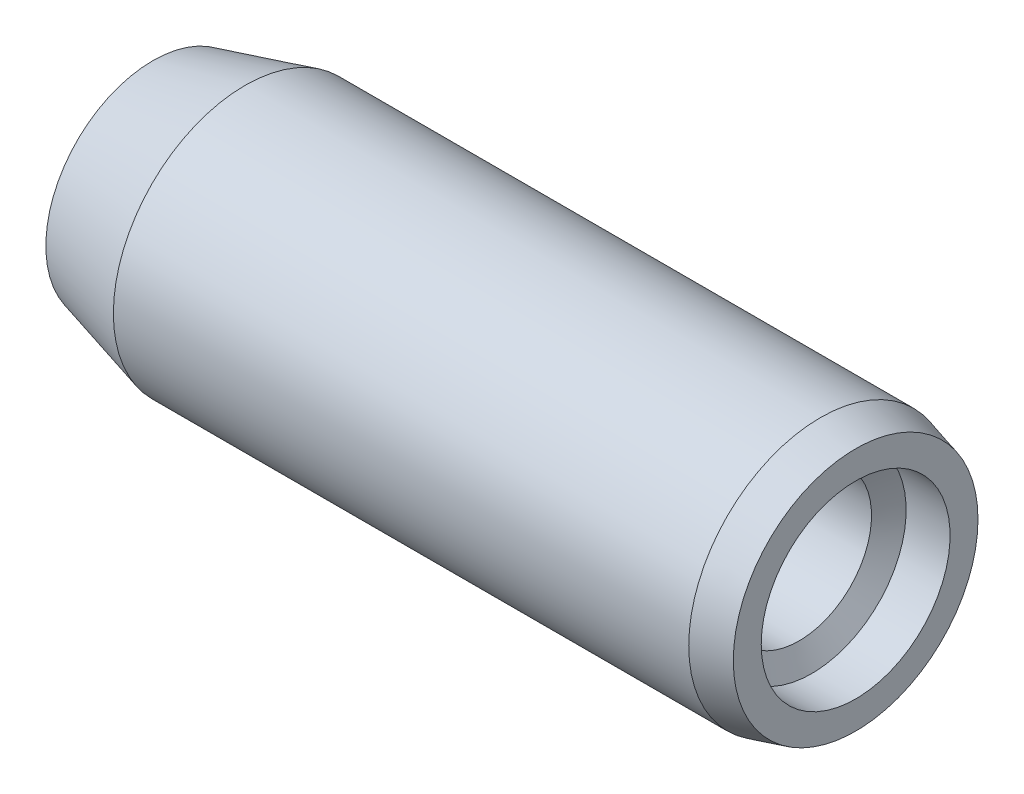
SolidWorks part; units mm, degrees
ref_plane "Front" through (0, 0, 0) normal (0, 0, 1) x (1, 0, 0)
ref_plane "Top" through (0, 0, 0) normal (0, 1, 0) x (1, 0, 0)
ref_plane "Right" through (0, 0, 0) normal (1, 0, 0) x (0, 0, -1)
sketch "Sketch1" plane through (0, 0, 0) normal (0, 0, 1) x (1, 0, 0)
  line L0 (0.5904, 2.5955) -> (0.5904, 0) construction
  line L1 (-3.8625, 0) -> (2.9703, 0) construction
  line L3 (0.5904, 2.5955) -> (2.1, 3)
  line L4 (2.1, 3) -> (15.2, 3)
  line L5 (15.2, 3) -> (16, 2.7856)
  line L6 (16, 2.7856) -> (16, 0)
  line L7 (16, 0) -> (0, 0)
  arc A0 (0.5904, 2.5955) -> (0, 0) centre (6, 0) ccw
  dimension "D1" = 6
  dimension "D3" = 15
  dimension "D7" = 75
revolve "Base-Revolve" add sketch "Sketch1" angle 360 about L1
sketch "Sketch2" plane through (0, 0, 0) normal (0, 0, 1) x (1, 0, 0)
  line L0 (0, 0) -> (0, 2.4373)
  line L1 (0, 2.4373) -> (2.1, 3)
  line L2 (2.1, 3) -> (15.2, 3)
  line L3 (15.2, 3) -> (16, 2.7856)
  line L4 (16, 2.7856) -> (16, 0)
  line L5 (16, 0) -> (0, 0)
  line L6 (0, 0) -> (-16.9805, 0) construction
  dimension "D1" = 6
  dimension "D2" = 15
  dimension "D3" = 75
  dimension "D4" = 16
  dimension "D5" = 0.8
  dimension "D6" = 2.1
revolve "Base-Revolve2" add sketch "Sketch2" angle 360 about L6
sketch "Sketch3" plane through (0, 0, 0) normal (0, 0, 1) x (1, 0, 0)
  line L0 (16, 0) -> (16, 2.15) construction
  line L1 (16, 2.15) -> (16.2, 2.15)
  line L2 (16, 2.15) -> (15, 2.15)
  line L3 (15, 2.15) -> (14.7113, 1.65)
  line L4 (14.7113, 1.65) -> (6, 1.65)
  line L5 (6, 1.65) -> (5.0474, 0)
  line L6 (5.0474, 0) -> (16, 0)
  line L7 (16, 0) -> (16.7399, 0) construction
  line L8 (16.2, 2.15) -> (16.2, 0)
  line L9 (16, -2.7856) -> (16, 2.7856) construction
  line L10 (16.2, 0) -> (16, 0)
  dimension "D4" = 60
  dimension "D5" = 60
revolve "TypeA" cut sketch "Sketch3" angle 360 about L7
cosmetic thread "ThreadCosmetic1" [suppressed] parameters "t1"=6, "d1"=4
sketch "Sketch4" plane through (0, 0, 0) normal (0, 0, 1) x (1, 0, 0)
  line L0 (0, 0) -> (22.7307, 0) construction
  line L1 (9.825, -1.3) -> (10.175, -1.3)
  line L2 (10.175, -1.3) -> (10.175, -1.65)
  line L3 (10.175, -1.65) -> (10, -1.9531)
  line L4 (10, -1.9531) -> (9.825, -1.65)
  line L5 (9.825, -1.3) -> (9.825, -1.65)
  line L6 (16, -2.15) -> (16, 2.15) construction
  dimension "D1" = 3.3
  dimension "D2" = 6
  dimension "D3" = 0.35
revolve "Cut-Revolve10" [suppressed] cut sketch "Sketch4" angle 360 about L0
pattern_linear "LPattern10" [suppressed] count 14 spacing 0.42 along (1, 0, 0) of bodies 104
equation "\"D1@Sketch1\" = \"d@Sketch1\""
equation "\"D6@Sketch2\" = \"c@Sketch1\""
equation "\"D4@Sketch2\" = \"l@Sketch1\""
equation "\"D1@Sketch2\" = \"d@Sketch1\""
equation "\"D5@Sketch2\" = \"a@Sketch1\""
equation "\"D1@Sketch4\" = \"d0@Sketch3\""
equation "\"D2@Sketch4\" = \"t1@ThreadCosmetic1\""
equation "\"D3@Sketch4\" = (  \"d1@ThreadCosmetic1\" - \"d0@Sketch3\" )  / 2"
equation "\"D3@LPattern10\" = \"D3@Sketch4\"*1.2"
equation "\"D1@LPattern10\" = \"t1@ThreadCosmetic1\" / \"D3@LPattern10\""
